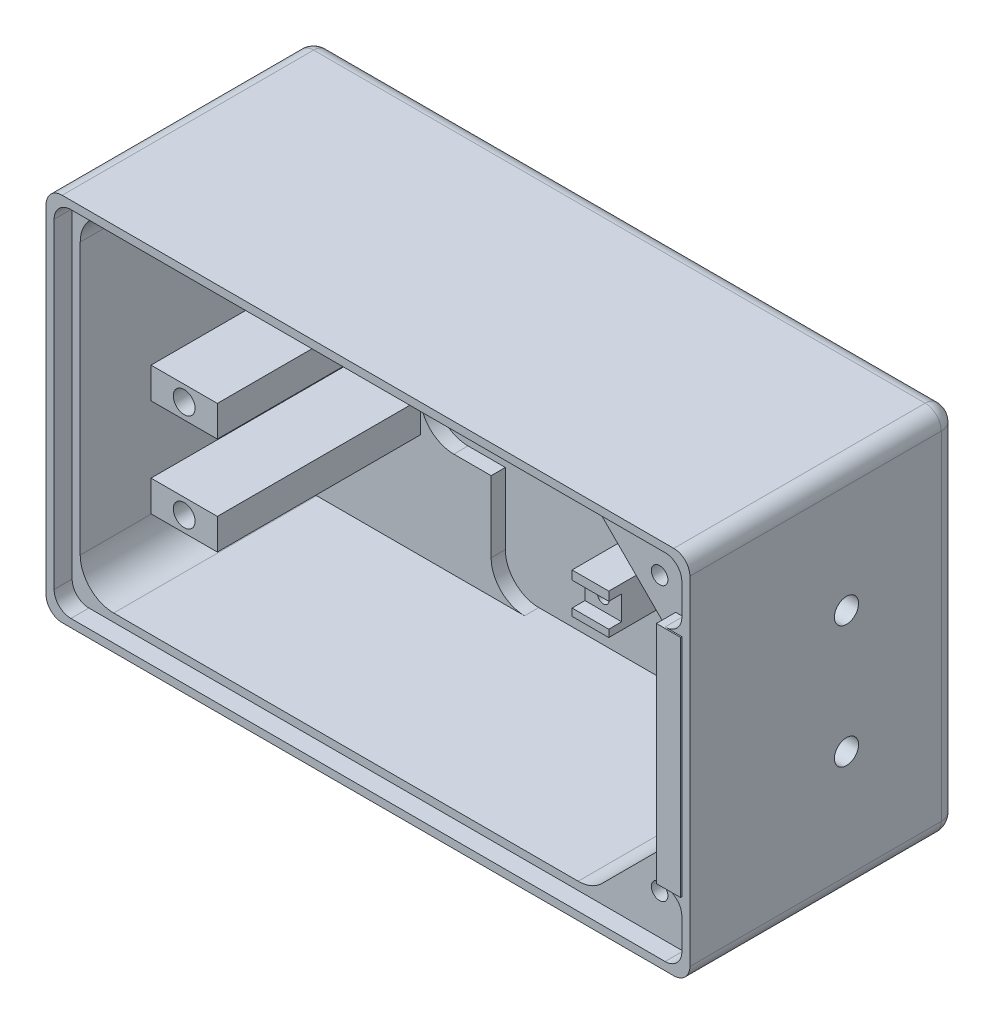
SolidWorks part; units mm, degrees
material "6061-T6 (SS)"
ref_plane "Front Plane" through (0, 0, 0) normal (0, 0, 1) x (1, 0, 0)
ref_plane "Top Plane" through (0, 0, 0) normal (0, 1, 0) x (1, 0, 0)
ref_plane "Right Plane" through (0, 0, 0) normal (1, 0, 0) x (0, 0, -1)
sketch "Sketch1" plane through (0, 0, 0) normal (0, 0, 1) x (1, 0, 0)
  line L1 (63.5, 36.5125) -> (-63.5, 36.5125)
  line L2 (63.5, 36.5125) -> (63.5, -36.5125)
  line L3 (63.5, -36.5125) -> (-63.5, -36.5125)
  line L4 (-63.5, 36.5125) -> (-63.5, -36.5125)
  line L5 (63.5, 36.5125) -> (-63.5, -36.5125) construction
  line L6 (63.5, -36.5125) -> (-63.5, 36.5125) construction
  point P0 (0, 0)
  dimension "D1" = 73.025
  dimension "D2" = 127
extrude "Boss-Extrude1" add sketch "Sketch1" along normal blind 38.1
sketch "Sketch2" plane through (0, 0, 38.1) normal (0, 0, 1) x (1, 0, 0)
  line L0 (63.5, -36.5125) -> (63.5, 36.5125) construction
  line L1 (56.515, -33.3375) -> (-16.51, -33.3375)
  line L2 (56.515, -33.3375) -> (56.515, 33.3375)
  line L3 (56.515, 33.3375) -> (-16.51, 33.3375)
  line L4 (-16.51, -33.3375) -> (-16.51, 33.3375)
  line L5 (56.515, -33.3375) -> (-16.51, 33.3375) construction
  line L6 (56.515, 33.3375) -> (-16.51, -33.3375) construction
  line L7 (63.5, 36.5125) -> (-63.5, 36.5125) construction
  line L8 (-70.2728, 0) -> (49929.7272, 0) construction
  line L9 (-60.325, 33.3375) -> (-45.085, 33.3375)
  line L10 (-60.325, 33.3375) -> (-60.325, -33.3375)
  line L11 (-60.325, -33.3375) -> (-45.085, -33.3375)
  line L12 (-45.085, 33.3375) -> (-45.085, -33.3375)
  line L13 (-63.5, 36.5125) -> (-63.5, -36.5125) construction
  point P0 (20.0025, 0)
  point P16 (-60.325, 0)
  point P17 (-45.085, 0)
  dimension "D1" = 6.985
  dimension "D2" = 3.175
  dimension "D3" = 3.175
  dimension "D4" = 3.175
  dimension "D5" = 28.575
  dimension "D6" = 73.025
extrude "Cut-Extrude1" cut sketch "Sketch2" against normal offset from surface (31.75 mm away) 6.35 up to face at (0, 0, 0)
sketch "Sketch3" plane through (0, 0, 38.1) normal (0, 0, 1) x (1, 0, 0)
  line L1 (-45.085, 33.3375) -> (-16.51, 33.3375)
  line L2 (-45.085, 33.3375) -> (-45.085, -33.3375)
  line L3 (-45.085, -33.3375) -> (-16.51, -33.3375)
  line L4 (-16.51, 33.3375) -> (-16.51, -33.3375)
extrude "Cut-Extrude2" cut sketch "Sketch3" against normal offset from surface (1.6206 mm away) 30.1294 up to face at (20.0025, 0, 6.35)
sketch "Sketch4" plane through (0, 0, 36.4794) normal (0, 0, 1) x (1, 0, 0)
  line L0 (0, 0) -> (50000, 0) construction
  line L1 (-16.51, -33.3375) -> (-3.81, -33.3375)
  line L2 (-16.51, -33.3375) -> (-16.51, -11.1125)
  line L3 (-16.51, -11.1125) -> (-3.81, -11.1125)
  line L4 (-3.81, -33.3375) -> (-3.81, -11.1125)
  line L5 (-3.81, 33.3375) -> (-3.81, 11.1125)
  line L6 (-16.51, 11.1125) -> (-3.81, 11.1125)
  line L7 (-16.51, 33.3375) -> (-16.51, 11.1125)
  line L8 (-16.51, 33.3375) -> (-3.81, 33.3375)
  line L9 (56.515, -33.3375) -> (56.515, 33.3375) construction
  dimension "D1" = 22.225
  dimension "D2" = 60.325
extrude "Boss-Extrude2" add sketch "Sketch4" against normal up to surface (30.1294 mm away) up to face at (20.0025, 0, 6.35)
sketch "Sketch5" plane through (0, 0, 36.4794) normal (0, 0, 1) x (1, 0, 0)
  line L0 (-60.325, -33.3375) -> (56.515, -33.3375) construction
  line L1 (-45.085, 33.3375) -> (-15.24, 33.3375)
  line L2 (-45.085, 33.3375) -> (-45.085, -33.3375)
  line L3 (-45.085, -33.3375) -> (-15.24, -33.3375)
  line L4 (-15.24, 33.3375) -> (-15.24, -33.3375)
  line L5 (-3.81, -33.3375) -> (-3.81, -11.1125) construction
  point P9 (-3.81, -22.225)
  dimension "D1" = 11.43
extrude "Cut-Extrude3" cut sketch "Sketch5" against normal up to surface (30.1294 mm away) up to face at (8.0962, 0, 6.35)
sketch "Sketch8" plane through (0, 0, 6.35) normal (0, 0, 1) x (1, 0, 0)
  line L0 (63.5, -36.5125) -> (63.5, 36.5125) construction
  line L1 (9.525, 15.875) -> (16.764, 15.875)
  line L2 (9.525, 15.875) -> (9.525, -15.875)
  line L3 (9.525, -15.875) -> (16.764, -15.875)
  line L4 (16.764, 15.875) -> (16.764, -15.875)
  line L5 (56.515, -33.3375) -> (56.515, 33.3375) construction
  point P4 (9.525, 0)
  dimension "D1" = 31.75
  dimension "D2" = 53.975
  dimension "D3" = 39.751
extrude "Boss-Extrude3" add sketch "Sketch8" along normal blind 17.9705
sketch "Sketch6" plane through (0, 0, 38.1) normal (0, 0, 1) x (1, 0, 0)
  line L0 (0, 0) -> (50000, 0) construction
  line L1 (6.35, 12.065) -> (53.975, 12.065) construction
  line L3 (6.35, 14.4462) -> (53.975, 14.4462)
  line L4 (6.35, 9.6837) -> (53.975, 9.6837)
  line L5 (63.5, -36.5125) -> (63.5, 36.5125) construction
  line L6 (6.35, -12.065) -> (53.975, -12.065) construction
  line L7 (6.35, -14.4462) -> (53.975, -14.4462)
  line L8 (6.35, -9.6837) -> (53.975, -9.6837)
  line L9 (9.525, 15.875) -> (9.525, -15.875) construction
  arc A0 (6.35, 14.4462) -> (6.35, 9.6837) centre (6.35, 12.065) ccw
  arc A1 (53.975, 9.6837) -> (53.975, 14.4462) centre (53.975, 12.065) ccw
  arc A2 (6.35, -14.4462) -> (6.35, -9.6837) centre (6.35, -12.065) cw
  arc A3 (53.975, -9.6837) -> (53.975, -14.4462) centre (53.975, -12.065) cw
  point P7 (30.1625, 12.065)
  point P16 (30.1625, -12.065)
  dimension "D1" = 2.3813
  dimension "D2" = 24.13
  dimension "D3" = 9.525
  dimension "D4" = 3.175
extrude "Cut-Extrude4" cut sketch "Sketch6" against normal offset from surface (18.6055 mm away) 13.1445 up to face at (-6.985, 0, 6.35)
fillet "Fillet1" [suppressed] radius 2.3813
sketch "Sketch7" plane through (0, 0, 38.1) normal (0, 0, 1) x (1, 0, 0)
  line L4 (-63.5, 36.5125) -> (-63.5, -36.5125)
  line L5 (-63.5, -36.5125) -> (63.5, -36.5125)
  line L6 (63.5, -36.5125) -> (63.5, 36.5125)
  line L7 (63.5, 36.5125) -> (-63.5, 36.5125)
  line L8 (-63.5, 36.5125) -> (-63.5, -36.5125)
  line L9 (-63.5, -36.5125) -> (63.5, -36.5125)
  line L10 (63.5, -36.5125) -> (63.5, 36.5125)
  line L11 (63.5, 36.5125) -> (-63.5, 36.5125)
  dimension "D1" = 0
extrude "Cut-Extrude5" cut sketch "Sketch7" against normal up to surface (1.6206 mm away) up to face at (-9.525, 22.225, 36.4794)
sketch "Sketch9" plane through (0, 0, 24.3205) normal (0, 0, 1) x (1, 0, 0)
  line L0 (16.764, -9.6837) -> (16.764, 9.6837) construction
  line L1 (-16.764, -7.9375) -> (16.764, -7.9375)
  line L2 (-16.764, -7.9375) -> (-16.764, 7.9375)
  line L3 (-16.764, 7.9375) -> (16.764, 7.9375)
  line L4 (16.764, -7.9375) -> (16.764, 7.9375)
  line L5 (-16.764, -7.9375) -> (16.764, 7.9375) construction
  line L6 (-16.764, 7.9375) -> (16.764, -7.9375) construction
  point P0 (0, 0)
  dimension "D1" = 15.875
extrude "Cut-Extrude6" cut sketch "Sketch9" against normal up to surface (17.9705 mm away) up to face at (-6.985, 0, 6.35)
sketch "Sketch10" plane through (0, 0, 36.4794) normal (0, 0, 1) x (1, 0, 0)
  line L0 (-3.81, -33.3375) -> (56.515, -33.3375) construction
  line L1 (-15.24, 33.3375) -> (-3.81, 33.3375)
  line L2 (-15.24, 33.3375) -> (-15.24, -33.3375)
  line L3 (-15.24, -33.3375) -> (-3.81, -33.3375)
  line L4 (63.5, 36.5125) -> (-63.5, 36.5125)
  line L5 (-63.5, 36.5125) -> (-63.5, -36.5125)
  line L6 (-63.5, -36.5125) -> (63.5, -36.5125)
  line L7 (63.5, -36.5125) -> (63.5, 36.5125)
  line L8 (63.5, 36.5125) -> (-63.5, 36.5125)
  line L9 (-63.5, 36.5125) -> (-63.5, -36.5125)
  line L10 (-63.5, -36.5125) -> (63.5, -36.5125)
  line L11 (63.5, -36.5125) -> (63.5, 36.5125)
  line L12 (-3.81, 33.3375) -> (-3.81, -33.3375)
  line L13 (-3.81, -33.3375) -> (56.515, -33.3375) construction
  dimension "D1" = 0
extrude "Cut-Extrude7" [suppressed] cut sketch "Sketch10" against normal up to surface (12.1589 mm away)
sketch "Sketch11" plane through (0, 0, 36.4794) normal (0, 0, 1) x (1, 0, 0)
  line L1 (-60.325, 33.3375) -> (56.515, 33.3375)
  line L2 (-60.325, 33.3375) -> (-60.325, -33.3375)
  line L3 (-60.325, -33.3375) -> (56.515, -33.3375)
  line L4 (63.5, 36.5125) -> (-63.5, 36.5125)
  line L5 (-63.5, 36.5125) -> (-63.5, -36.5125)
  line L6 (-63.5, -36.5125) -> (63.5, -36.5125)
  line L7 (63.5, -36.5125) -> (63.5, 36.5125)
  line L8 (63.5, 36.5125) -> (-63.5, 36.5125)
  line L9 (-63.5, 36.5125) -> (-63.5, -36.5125)
  line L10 (-63.5, -36.5125) -> (63.5, -36.5125)
  line L11 (63.5, -36.5125) -> (63.5, 36.5125)
  line L26 (56.515, -33.3375) -> (56.515, 33.3375) construction
  line L27 (56.515, -33.3375) -> (56.515, 33.3375)
  dimension "D1" = 0
extrude "Boss-Extrude4" add sketch "Sketch11" along normal blind 12.7331
hole_wizard "#4-40 Tapped Hole1" positions "Sketch12" profile "Sketch13" tap size "#4-40" standard "ANSI Inch"
sketch "Sketch12" plane through (0, 0, 36.4794) normal (0, 0, 1) x (1, 0, 0)
  line L0 (0, 0) -> (-50000, 0) construction
  line L1 (-9.525, 11.1125) -> (-9.525, -49988.8875) construction
  line L2 (-15.24, 11.1125) -> (-3.81, 11.1125) construction
  point P0 (-9.525, 19)
  point P10 (-9.525, 11.1125)
  point P15 (-9.525, -19)
  dimension "D1" = 38
sketch "Sketch13" plane through (-9.525, 19, 36.4794) normal (1, 0, 0) x (0, -1, 0)
  line L0 (0, 0) -> (0, 8.2992)
  line L1 (0, 8.2992) -> (1.1303, 7.62)
  line L2 (1.1303, 7.62) -> (1.1303, 0)
  line L5 (1.1303, 0) -> (0, 0)
  line L10 (0, 8.2992) -> (-1.1303, 7.62) construction
  line L11 (0, -6.35) -> (0, 107.95) construction
  dimension "Tap Drill Dia." = 2.2606
  dimension "Tap Drill Depth" = 7.62
  dimension "Drill Angle" = 118
cosmetic thread "Hole Thread1" parameters "D1"=5.588, "D2"=2.8448
cosmetic thread "Hole Thread2" parameters "D1"=5.588, "D2"=2.8448
chamfer "Chamfer1" distance 15.875 angle 45 2 edges at (56.515, 33.3375, 27.7812) (56.515, -33.3375, 27.7812)
fillet "Fillet2" radius 6.604 10 edges at (-60.325, -33.3375, 27.7812) (-3.81, -33.3375, 21.4147) (-15.24, -33.3375, 21.4147) (-15.24, 33.3375, 21.4147) (-3.81, 33.3375, 21.4147) (-60.325, 33.3375, 27.7812) (56.515, 17.4625, 27.7812) (40.64, 33.3375, 27.7812) (56.515, -17.4625, 27.7812) (40.64, -33.3375, 27.7812)
sketch "Sketch14" plane through (0, 0, 36.4794) normal (0, 0, 1) x (1, 0, 0)
  line L0 (-15.24, -11.1125) -> (-15.24, -26.7335) construction
  line L1 (-21.844, -33.3375) -> (2.794, -33.3375) construction
  line L2 (-3.81, -26.7335) -> (-3.81, -11.1125) construction
  line L3 (-3.81, -11.1125) -> (-15.24, -11.1125) construction
  line L4 (-3.81, 11.1125) -> (-3.81, 26.7335) construction
  line L5 (2.794, 33.3375) -> (-21.844, 33.3375) construction
  line L6 (-15.24, 26.7335) -> (-15.24, 11.1125) construction
  line L7 (-15.24, 11.1125) -> (-3.81, 11.1125) construction
  line L8 (-15.24, -11.1125) -> (-15.24, -26.7335)
  line L9 (-21.844, -33.3375) -> (2.794, -33.3375)
  line L10 (-3.81, -26.7335) -> (-3.81, -11.1125)
  line L11 (-3.81, -11.1125) -> (-15.24, -11.1125)
  line L12 (-3.81, 11.1125) -> (-3.81, 26.7335)
  line L13 (2.794, 33.3375) -> (-21.844, 33.3375)
  line L14 (-15.24, 26.7335) -> (-15.24, 11.1125)
  line L15 (-15.24, 11.1125) -> (-3.81, 11.1125)
  arc A0 (-21.844, -33.3375) -> (-15.24, -26.7335) centre (-21.844, -26.7335) ccw construction
  arc A1 (-3.81, -26.7335) -> (2.794, -33.3375) centre (2.794, -26.7335) ccw construction
  arc A2 (2.794, 33.3375) -> (-3.81, 26.7335) centre (2.794, 26.7335) ccw construction
  arc A3 (-15.24, 26.7335) -> (-21.844, 33.3375) centre (-21.844, 26.7335) ccw construction
  arc A4 (-21.844, -33.3375) -> (-15.24, -26.7335) centre (-21.844, -26.7335) ccw
  arc A5 (-3.81, -26.7335) -> (2.794, -33.3375) centre (2.794, -26.7335) ccw
  arc A6 (2.794, 33.3375) -> (-3.81, 26.7335) centre (2.794, 26.7335) ccw
  arc A7 (-15.24, 26.7335) -> (-21.844, 33.3375) centre (-21.844, 26.7335) ccw
extrude "Cut-Extrude8" cut sketch "Sketch14" against normal up to surface (30.1294 mm away) up to face at (13.1445, 11.9062, 6.35)
sketch "Sketch15" plane through (0, 0, 6.35) normal (0, 0, 1) x (1, 0, 0)
  line L0 (-60.325, 26.7335) -> (-60.325, -26.7335) construction
  line L1 (-60.325, 12.7) -> (-19.325, 12.7)
  line L2 (-60.325, 12.7) -> (-60.325, 33.3375)
  line L3 (-60.325, 33.3375) -> (-19.325, 33.3375)
  line L4 (-19.325, 12.7) -> (-19.325, 33.3375)
  line L5 (37.9045, 33.3375) -> (-53.721, 33.3375) construction
  line L6 (0, 0) -> (-50000, 0) construction
  line L7 (-19.325, -12.7) -> (-19.325, -33.3375)
  line L8 (-60.325, -33.3375) -> (-19.325, -33.3375)
  line L9 (-60.325, -12.7) -> (-60.325, -33.3375)
  line L10 (-60.325, -12.7) -> (-19.325, -12.7)
  dimension "D1" = 25.4
  dimension "D2" = 41
extrude "Boss-Extrude5" add sketch "Sketch15" along normal blind 2.8035
sketch "Sketch16" plane through (0, 0, 6.35) normal (0, 0, 1) x (1, 0, 0)
  line L0 (-60.325, 12.7) -> (-19.325, 12.7) construction
  line L1 (-46.355, 12.7) -> (-33.274, 12.7)
  line L2 (-46.355, 12.7) -> (-46.355, 6.604)
  line L3 (-46.355, 6.604) -> (-33.274, 6.604)
  line L4 (-33.274, 12.7) -> (-33.274, 6.604)
  line L5 (0, 0) -> (50000, 0) construction
  line L6 (-60.325, 12.7) -> (-60.325, -12.7) construction
  line L7 (-33.274, -12.7) -> (-33.274, -6.604)
  line L8 (-46.355, -6.604) -> (-33.274, -6.604)
  line L9 (-46.355, -12.7) -> (-46.355, -6.604)
  line L10 (-46.355, -12.7) -> (-33.274, -12.7)
  dimension "D1" = 13.97
  dimension "D2" = 13.208
  dimension "D3" = 13.081
extrude "Boss-Extrude6" add sketch "Sketch16" along normal up to surface (42.8625 mm away) up to face at (0, 0, 49.2125)
fillet "Fillet3" radius 6.604 8 edges at (-19.325, -33.3375, 7.7517) (-19.325, 33.3375, 7.7517) (-33.274, 12.7, 7.7517) (-33.274, -12.7, 7.7517) (-46.355, -12.7, 7.7517) (-60.325, -12.7, 7.7517) (-46.355, 12.7, 7.7517) (-60.325, 12.7, 7.7517)
fillet "Fillet4" radius 3.175 8 edges at (63.5, -36.5125, 24.6062) (63.5, 36.5125, 24.6062) (-63.5, 36.5125, 24.6062) (-63.5, -36.5125, 24.6062) (0, -36.5125, 0) (63.5, 0, 0) (0, 36.5125, 0) (-63.5, 0, 0)
hole_wizard "CSK for #8 Flat Head Socket Cap Screw1" positions "Sketch19" profile "Sketch18" countersink size "#8" standard "ANSI Inch" end condition through all
sketch "Sketch19" plane through (0, 0, 0) normal (0, 0, -1) x (-1, 0, 0)
  line L0 (0, 0) -> (50000, 0) construction
  line L2 (33.274, -12.7) -> (46.355, -12.7) construction
  line L3 (39.8145, -12.7) -> (39.8145, -6.604) construction
  line L4 (33.274, -6.604) -> (46.355, -6.604) construction
  point P0 (39.8145, -9.652)
  point P7 (39.8145, 9.652)
sketch "Sketch18" plane through (-39.8145, -9.652, 0) normal (1, 0, 0) x (0, 1, 0)
  line L0 (0, 0) -> (0, 49.2125)
  line L1 (0, 49.2125) -> (2.1526, 49.2125)
  line L2 (2.1526, 49.2125) -> (2.1526, 2.7685)
  line L3 (2.1526, 2.7685) -> (4.5593, 0)
  line L5 (4.5593, 0) -> (0, 0)
  line L6 (-2.1526, 2.7685) -> (-4.5593, 0) construction
  line L11 (0, -6.35) -> (0, 107.95) construction
  dimension "Thru Hole Dia." = 4.3053
  dimension "Thru Hole Depth" = 49.2125
  dimension "Near C'Sink Dia." = 9.1186
  dimension "Near C'Sink Angle" = 82
sketch "Sketch22" plane through (63.5, 0, 0) normal (1, 0, 0) x (0, 0, -1)
  line L2 (0, 0) -> (50000, 0) construction
  line L3 (-19.4945, 14.4462) -> (-19.4945, 9.6837) construction
  circle A0 centre (-21.8758, -12.065) radius 2.3876
  circle A1 centre (-21.8758, 12.065) radius 2.3876
  dimension "D1" = 4.7752
  dimension "D2" = 24.13
  dimension "D3" = 2.3813
extrude "Cut-Extrude9" cut sketch "Sketch22" against normal up to next
hole_wizard "#4-40 Tapped Hole3" positions "Sketch26" profile "Sketch27" tap size "#4-40" standard "ANSI Inch"
sketch "Sketch26" plane through (0, 0, 24.3205) normal (0, 0, 1) x (1, 0, 0)
  line L2 (0, 0) -> (50000, 0) construction
  line L4 (16.764, 15.875) -> (9.525, 15.875) construction
  point P0 (13.1445, 12.065)
  point P4 (13.1445, -12.065)
  point P20 (13.1445, 15.875)
  dimension "D1" = 24.13
sketch "Sketch27" plane through (13.1445, 12.065, 24.3205) normal (1, 0, 0) x (0, -1, 0)
  line L0 (0, 0) -> (0, 13.3792)
  line L1 (0, 13.3792) -> (1.1303, 12.7)
  line L2 (1.1303, 12.7) -> (1.1303, 0)
  line L5 (1.1303, 0) -> (0, 0)
  line L10 (0, 13.3792) -> (-1.1303, 12.7) construction
  line L11 (0, -6.35) -> (0, 107.95) construction
  dimension "Tap Drill Dia." = 2.2606
  dimension "Tap Drill Depth" = 12.7
  dimension "Drill Angle" = 118
cosmetic thread "Hole Thread30" parameters "D1"=10.668, "D2"=2.8448
cosmetic thread "Hole Thread31" parameters "D1"=10.668, "D2"=2.8448
hole_wizard "CBORE for #4 Socket Head Cap Screw1" positions "Sketch28" profile "Sketch29" counterbore size "#4" standard "ANSI Inch" end condition through all
sketch "Sketch28" plane through (0, 0, 0) normal (0, 0, -1) x (-1, 0, 0)
  line L0 (0, 0) -> (-50000, 0) construction
  line L1 (-63.5, -33.3375) -> (-63.5, 33.3375) construction
  line L2 (60.325, -36.5125) -> (-60.325, -36.5125) construction
  point P0 (-53.975, -26.9875)
  point P7 (-53.975, 26.9875)
  dimension "D1" = 9.525
  dimension "D2" = 9.525
sketch "Sketch29" plane through (53.975, -26.9875, 0) normal (1, 0, 0) x (0, 1, 0)
  line L0 (0, 0) -> (0, 49.2125)
  line L1 (0, 49.2125) -> (1.6319, 49.2125)
  line L3 (1.6319, 49.2125) -> (1.632, 12.4968)
  line L4 (1.632, 12.4968) -> (3.175, 12.4968)
  line L5 (3.175, 12.4968) -> (3.175, 0)
  line L7 (3.175, 0) -> (0, 0)
  line L11 (0, -6.35) -> (0, 107.95) construction
  dimension "Thru Hole Dia." = 3.2639
  dimension "Thru Hole Depth" = 49.2125
  dimension "C'Bore Dia." = 6.35
  dimension "C'Bore Depth" = 12.4968
sketch "Sketch30" plane through (0, 0, 0) normal (0, 0, -1) x (-1, 0, 0)
  line L0 (0, 0) -> (-50000, 0) construction
  line L1 (60.325, -36.5125) -> (-60.325, -36.5125) construction
  line L2 (63.5, 33.3375) -> (63.5, -33.3375) construction
  circle A0 centre (53.975, -26.9875) radius 3.175
  circle A1 centre (53.975, 26.9875) radius 3.175
  dimension "D1" = 9.525
  dimension "D2" = 6.35
  dimension "D3" = 9.525
extrude "Cut-Extrude10" cut sketch "Sketch30" against normal blind 9.525
sketch "Sketch31" plane through (0, 0, 49.2125) normal (0, 0, 1) x (1, 0, 0)
  line L1 (57.15, 22.225) -> (63.5, 22.225)
  line L2 (57.15, 22.225) -> (57.15, -22.225)
  line L3 (57.15, -22.225) -> (63.5, -22.225)
  line L4 (63.5, 22.225) -> (63.5, -22.225)
  line L5 (63.5, -33.3375) -> (63.5, 33.3375) construction
  line L6 (56.515, -14.727) -> (56.515, 14.727) construction
  point P8 (57.15, 0)
  dimension "D1" = 44.45
  dimension "D2" = 0.635
extrude "Boss-Extrude7" add sketch "Sketch31" along normal blind 3.81
fillet "Fillet5" [suppressed] radius 3.175
sketch "Sketch32" plane through (0, 0, 24.3205) normal (0, 0, 1) x (1, 0, 0)
  line L1 (9.525, 15.875) -> (16.764, 15.875)
  line L2 (9.525, 15.875) -> (9.525, -15.875)
  line L3 (9.525, -15.875) -> (16.764, -15.875)
  line L4 (16.764, 15.875) -> (16.764, -15.875)
extrude "Cut-Extrude11" cut sketch "Sketch32" against normal blind 2.286
sketch "Sketch33" plane through (0, 0, 9.1535) normal (0, 0, 1) x (1, 0, 0)
  line L0 (-33.274, -6.604) -> (-46.355, -6.604) construction
  line L1 (-46.355, 6.604) -> (-33.274, 6.604) construction
  line L2 (-60.325, 6.096) -> (-60.325, -6.096) construction
  line L3 (-33.274, -6.604) -> (-46.355, -6.604)
  line L4 (-46.355, 6.604) -> (-33.274, 6.604)
  line L5 (-60.325, 6.096) -> (-60.325, -6.096)
  line L6 (-53.721, 12.7) -> (-52.9394, 12.7) construction
  line L7 (-52.9394, -12.7) -> (-53.721, -12.7) construction
  line L8 (-53.721, 12.7) -> (-52.9394, 12.7)
  line L9 (-52.9394, -12.7) -> (-53.721, -12.7)
  line L10 (-33.274, 6.604) -> (-33.274, -6.604)
  arc A0 (-52.9394, -12.7) -> (-46.355, -6.604) centre (-52.9394, -6.096) ccw construction
  arc A1 (-60.325, -6.096) -> (-53.721, -12.7) centre (-53.721, -6.096) ccw construction
  arc A2 (-46.355, 6.604) -> (-52.9394, 12.7) centre (-52.9394, 6.096) ccw construction
  arc A3 (-53.721, 12.7) -> (-60.325, 6.096) centre (-53.721, 6.096) ccw construction
  arc A4 (-52.9394, -12.7) -> (-46.355, -6.604) centre (-52.9394, -6.096) ccw
  arc A5 (-60.325, -6.096) -> (-53.721, -12.7) centre (-53.721, -6.096) ccw
  arc A6 (-46.355, 6.604) -> (-52.9394, 12.7) centre (-52.9394, 6.096) ccw
  arc A7 (-53.721, 12.7) -> (-60.325, 6.096) centre (-53.721, 6.096) ccw
extrude "Boss-Extrude9" add sketch "Sketch33" against normal up to surface (2.8035 mm away) up to face at (13.1445, 11.9062, 6.35)
sketch "Sketch34" plane through (0, 0, 49.2125) normal (0, 0, 1) x (1, 0, 0)
  line L0 (61.9125, 22.225) -> (61.9125, 33.3375)
  line L1 (60.325, 34.925) -> (-60.325, 34.925)
  line L2 (-61.9125, 33.3375) -> (-61.9125, -33.3375)
  line L3 (-60.325, -34.925) -> (60.325, -34.925)
  line L4 (61.9125, -33.3375) -> (61.9125, -22.225)
  line L5 (61.9125, 22.225) -> (63.5, 22.225)
  line L6 (61.9125, -22.225) -> (63.5, -22.225)
  line L8 (57.15, 22.225) -> (63.5, 22.225)
  line L9 (63.5, 22.225) -> (63.5, 33.3375)
  line L10 (60.325, 36.5125) -> (-60.325, 36.5125)
  line L11 (-63.5, 33.3375) -> (-63.5, -33.3375)
  line L12 (-60.325, -36.5125) -> (60.325, -36.5125)
  line L13 (63.5, -33.3375) -> (63.5, -22.225)
  line L14 (63.5, -22.225) -> (57.15, -22.225)
  line L15 (57.15, -22.225) -> (57.15, 22.225)
  line L17 (63.5, 22.225) -> (63.5, 33.3375)
  line L18 (60.325, 36.5125) -> (-60.325, 36.5125)
  line L19 (-63.5, 33.3375) -> (-63.5, -33.3375)
  line L20 (-60.325, -36.5125) -> (60.325, -36.5125)
  line L21 (63.5, -33.3375) -> (63.5, -22.225)
  arc A0 (61.9125, 33.3375) -> (60.325, 34.925) centre (60.325, 33.3375) ccw
  arc A1 (-60.325, 34.925) -> (-61.9125, 33.3375) centre (-60.325, 33.3375) ccw
  arc A2 (-61.9125, -33.3375) -> (-60.325, -34.925) centre (-60.325, -33.3375) ccw
  arc A3 (60.325, -34.925) -> (61.9125, -33.3375) centre (60.325, -33.3375) ccw
  arc A4 (63.5, 33.3375) -> (60.325, 36.5125) centre (60.325, 33.3375) ccw
  arc A5 (-60.325, 36.5125) -> (-63.5, 33.3375) centre (-60.325, 33.3375) ccw
  arc A6 (-63.5, -33.3375) -> (-60.325, -36.5125) centre (-60.325, -33.3375) ccw
  arc A7 (60.325, -36.5125) -> (63.5, -33.3375) centre (60.325, -33.3375) ccw
  arc A8 (63.5, 33.3375) -> (60.325, 36.5125) centre (60.325, 33.3375) ccw
  arc A9 (-60.325, 36.5125) -> (-63.5, 33.3375) centre (-60.325, 33.3375) ccw
  arc A10 (-63.5, -33.3375) -> (-60.325, -36.5125) centre (-60.325, -33.3375) ccw
  arc A11 (60.325, -36.5125) -> (63.5, -33.3375) centre (60.325, -33.3375) ccw
  dimension "D1" = 0
  dimension "D2" = 1.5875
extrude "Boss-Extrude10" add sketch "Sketch34" along normal up to surface (3.81 mm away) up to face at (60.325, 0, 53.0225)
sketch "Sketch35" plane through (0, 0, 53.0225) normal (0, 0, 1) x (1, 0, 0)
  line L0 (-61.9125, -33.3375) -> (-61.9125, 33.3375) construction
  line L1 (-60.325, 34.925) -> (60.325, 34.925) construction
  line L2 (-60.325, 34.925) -> (60.325, 34.925) construction
  line L3 (-58.6105, 34.925) -> (-61.9125, 34.925)
  line L4 (-61.9125, 34.925) -> (-61.9125, 31.623)
  line L5 (0, 0) -> (50000, 0) construction
  line L6 (61.9125, 22.225) -> (57.15, 22.225) construction
  line L7 (61.9125, 33.3375) -> (61.9125, 22.225) construction
  line L8 (61.9125, 33.3375) -> (61.9125, 22.225) construction
  line L9 (61.9125, 22.225) -> (57.15, 22.225) construction
  line L10 (58.6105, 34.925) -> (61.9125, 34.925)
  line L11 (61.9125, 34.925) -> (61.9125, 31.623)
  line L12 (61.9125, 25.527) -> (61.9125, 22.225)
  line L13 (61.9125, 22.225) -> (58.6105, 22.225)
  line L14 (61.9125, -22.225) -> (58.6105, -22.225)
  line L15 (61.9125, -25.527) -> (61.9125, -22.225)
  line L16 (61.9125, -34.925) -> (61.9125, -31.623)
  line L17 (58.6105, -34.925) -> (61.9125, -34.925)
  line L18 (-61.9125, -34.925) -> (-61.9125, -31.623)
  line L19 (-58.6105, -34.925) -> (-61.9125, -34.925)
  arc A0 (-61.9125, 31.623) -> (-58.6105, 34.925) centre (-58.6105, 31.623) cw
  arc A1 (58.6105, 22.225) -> (61.9125, 25.527) centre (58.6105, 25.527) ccw
  arc A2 (58.6105, 34.925) -> (61.9125, 31.623) centre (58.6105, 31.623) cw
  arc A3 (58.6105, -34.925) -> (61.9125, -31.623) centre (58.6105, -31.623) ccw
  arc A4 (58.6105, -22.225) -> (61.9125, -25.527) centre (58.6105, -25.527) cw
  arc A5 (-61.9125, -31.623) -> (-58.6105, -34.925) centre (-58.6105, -31.623) ccw
  dimension "D1" = 3.302
extrude "Boss-Extrude11" add sketch "Sketch35" against normal up to surface (3.81 mm away) up to face at (52.3431, 26.9875, 49.2125)
sketch "Sketch36" plane through (0, 0, 53.0225) normal (0, 0, 1) x (1, 0, 0)
  line L0 (57.15, 22.225) -> (57.15, -22.225) construction
  line L1 (61.9125, 22.225) -> (57.15, 22.225)
  line L2 (61.9125, 22.225) -> (61.9125, -22.225)
  line L3 (61.9125, -22.225) -> (57.15, -22.225)
  line L4 (63.5, -33.3375) -> (63.5, 33.3375)
  line L5 (60.325, 36.5125) -> (-60.325, 36.5125)
  line L6 (-63.5, 33.3375) -> (-63.5, -33.3375)
  line L7 (-60.325, -36.5125) -> (60.325, -36.5125)
  line L8 (63.5, -33.3375) -> (63.5, 33.3375)
  line L9 (60.325, 36.5125) -> (-60.325, 36.5125)
  line L10 (-63.5, 33.3375) -> (-63.5, -33.3375)
  line L11 (-60.325, -36.5125) -> (60.325, -36.5125)
  line L12 (57.15, 22.225) -> (57.15, -22.225)
  line L13 (61.9125, -25.527) -> (61.9125, -31.623) construction
  line L14 (57.15, -22.225) -> (58.6105, -22.225) construction
  line L15 (57.15, -22.225) -> (58.6105, -22.225) construction
  arc A4 (60.325, -36.5125) -> (63.5, -33.3375) centre (60.325, -33.3375) ccw
  arc A5 (63.5, 33.3375) -> (60.325, 36.5125) centre (60.325, 33.3375) ccw
  arc A6 (-60.325, 36.5125) -> (-63.5, 33.3375) centre (-60.325, 33.3375) ccw
  arc A7 (-63.5, -33.3375) -> (-60.325, -36.5125) centre (-60.325, -33.3375) ccw
  arc A8 (60.325, -36.5125) -> (63.5, -33.3375) centre (60.325, -33.3375) ccw
  arc A9 (63.5, 33.3375) -> (60.325, 36.5125) centre (60.325, 33.3375) ccw
  arc A10 (-60.325, 36.5125) -> (-63.5, 33.3375) centre (-60.325, 33.3375) ccw
  arc A11 (-63.5, -33.3375) -> (-60.325, -36.5125) centre (-60.325, -33.3375) ccw
  dimension "D1" = 0
extrude "Cut-Extrude12" cut sketch "Sketch36" against normal blind 0.254
sketch "Sketch37" plane through (0, 0, 49.2125) normal (0, 0, 1) x (1, 0, 0)
  line L0 (-33.274, -12.7) -> (-33.274, -6.604) construction
  line L1 (-46.355, 12.7) -> (-33.274, 12.7)
  line L2 (-46.355, 12.7) -> (-46.355, -12.7)
  line L3 (-46.355, -12.7) -> (-33.274, -12.7)
  line L4 (-33.274, 12.7) -> (-33.274, -12.7)
extrude "Cut-Extrude13" [suppressed] cut sketch "Sketch37" against normal blind 9.525
sketch "Sketch38" plane through (0, 0, 6.35) normal (0, 0, 1) x (1, 0, 0)
  line L0 (-26.67, 0) -> (26.67, 0) construction
  line L1 (-26.67, 6.604) -> (26.67, 6.604)
  line L2 (-26.67, -6.604) -> (26.67, -6.604)
  line L3 (-33.274, -6.604) -> (-33.274, 6.604) construction
  arc A0 (-26.67, 6.604) -> (-26.67, -6.604) centre (-26.67, 0) ccw
  arc A1 (26.67, -6.604) -> (26.67, 6.604) centre (26.67, 0) ccw
  point P3 (0, 0)
  dimension "D1" = 6.604
extrude "Cut-Extrude14" cut sketch "Sketch38" against normal blind 1.5875
sketch "Sketch39" plane through (0, 0, 0) normal (0, 0, -1) x (-1, 0, 0)
  line L1 (29.2417, -13.4937) -> (-41.9417, -13.4938)
  line L2 (32.5437, -10.1917) -> (32.5437, 10.1917)
  line L3 (29.2417, 13.4938) -> (-41.9417, 13.4937)
  line L4 (-45.2437, -10.1917) -> (-45.2437, 10.1917)
  line L5 (32.5437, -13.4937) -> (-45.2437, 13.4937) construction
  line L6 (32.5437, 13.4938) -> (-45.2437, -13.4938) construction
  arc A0 (-41.9417, -13.4938) -> (-45.2437, -10.1917) centre (-41.9417, -10.1918) cw
  arc A1 (32.5437, 10.1917) -> (29.2417, 13.4938) centre (29.2417, 10.1918) ccw
  arc A2 (29.2417, -13.4937) -> (32.5437, -10.1917) centre (29.2417, -10.1917) ccw
  arc A3 (-41.9417, 13.4937) -> (-45.2437, 10.1917) centre (-41.9417, 10.1917) ccw
  point P0 (-6.35, 0)
  dimension "D4" = 3.302
  dimension "D1" = 77.7875
  dimension "D2" = 26.9875
  dimension "D3" = 6.35
extrude "Cut-Extrude15" cut sketch "Sketch39" against normal blind 0.254
